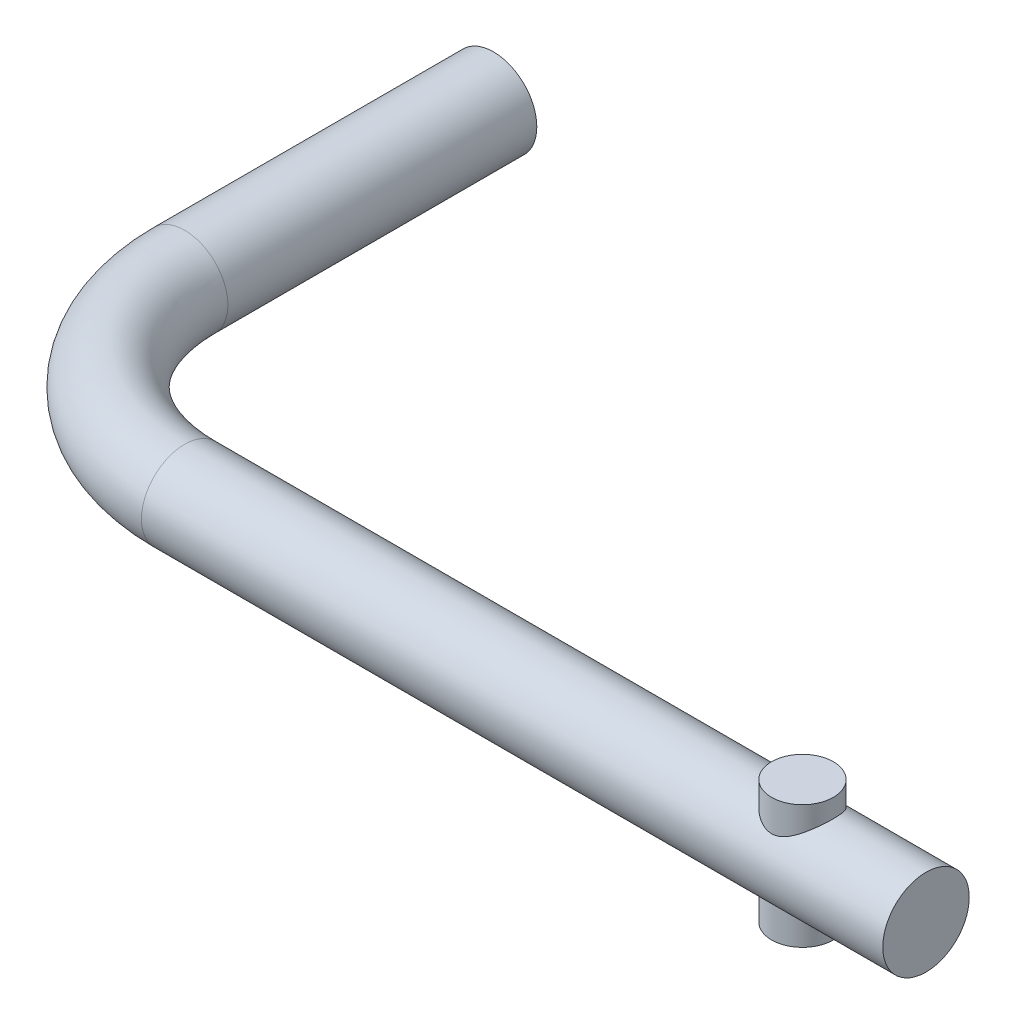
SolidWorks part; units mm, degrees
ref_plane "Front Plane" through (0, 0, 0) normal (0, 0, 1) x (1, 0, 0)
ref_plane "Top Plane" through (0, 0, 0) normal (0, 1, 0) x (1, 0, 0)
ref_plane "Right Plane" through (0, 0, 0) normal (1, 0, 0) x (0, 0, -1)
sketch "Sketch1" plane through (0, 0, 0) normal (0, 1, 0) x (1, 0, 0)
  line L0 (0, 0) -> (-120, 0)
  line L1 (-150, 30) -> (-150, 80)
  arc A0 (-120, 0) -> (-150, 30) centre (-120, 30) cw
  point P6 (-150, 0)
  dimension "D3" = 30
  dimension "D1" = 150
  dimension "D2" = 80
sweep "Sweep1" add path "Sketch1" circular profile diameter 14 parameters "D3"=14
sketch "Sketch8" plane through (0, 0, 0) normal (0, 1, 0) x (1, 0, 0)
  line L0 (0, 0) -> (-120, 0) construction
  line L1 (0, -7) -> (0, 7) construction
  circle A0 centre (-20, 0) radius 5
  dimension "D1" = 10
  dimension "D2" = 20
extrude "Boss-Extrude1" add sketch "Sketch8" along normal blind 10 and the other way blind 10
